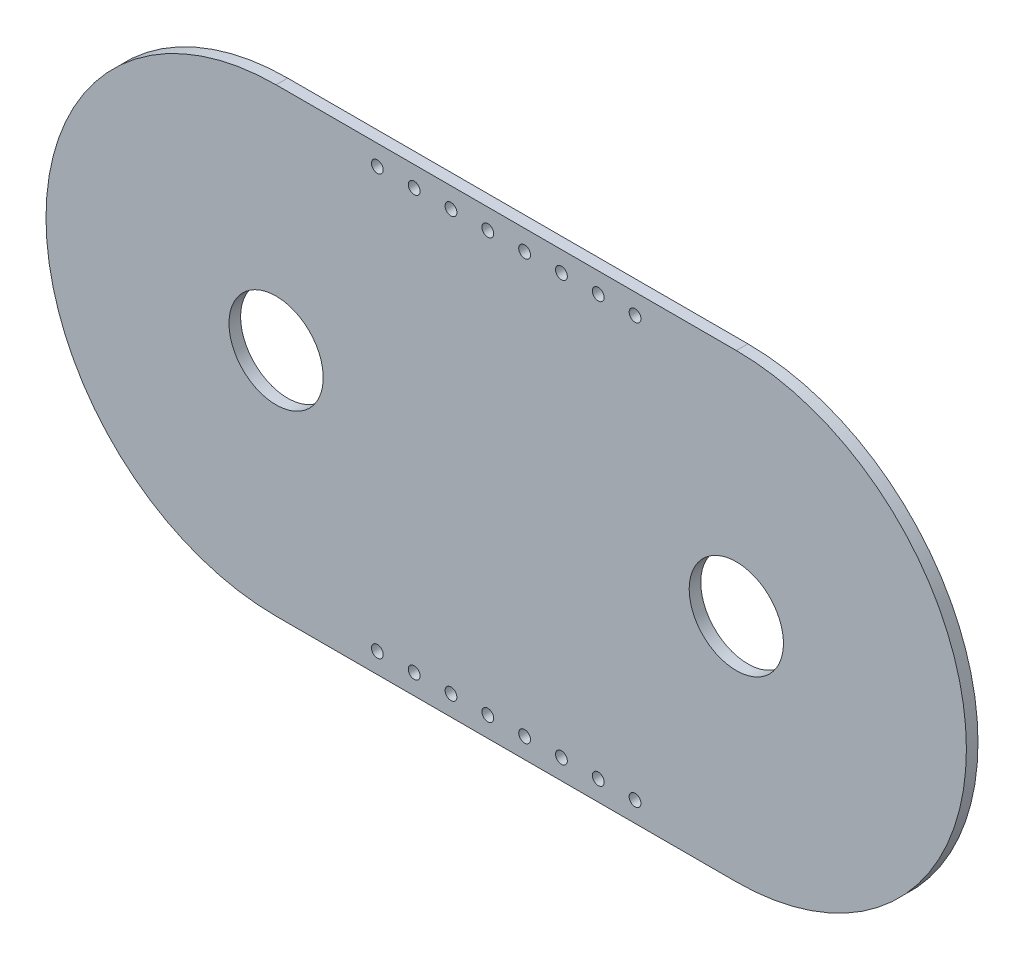
SolidWorks part; units mm, degrees
ref_plane "Front Plane" through (0, 0, 0) normal (0, 0, 1) x (1, 0, 0)
ref_plane "Top Plane" through (0, 0, 0) normal (0, 1, 0) x (1, 0, 0)
ref_plane "Right Plane" through (0, 0, 0) normal (1, 0, 0) x (0, 0, -1)
sketch "Sketch1" plane through (0, 0, 0) normal (0, 0, 1) x (1, 0, 0)
  line L0 (-15.875, 15.875) -> (47.625, 15.875) construction
  line L3 (0, 31.75) -> (31.75, 31.75)
  line L5 (0, 0) -> (31.75, 0)
  line L7 (15.875, 31.75) -> (15.875, 0) construction
  arc A40 (0, 31.75) -> (0, 0) centre (0, 15.875) ccw
  arc A41 (31.75, 0) -> (31.75, 31.75) centre (31.75, 15.875) ccw
  circle A42 centre (0, 15.875) radius 3.2512
  circle A43 centre (31.75, 15.875) radius 3.2512
  point P29 (0, 15.875)
  dimension "D2" = 31.75
  dimension "D4" = 6.5024
  dimension "D1" = 31.75
  dimension "D3" = 6.5024
extrude "Boss-Extrude1" add sketch "Sketch1" along normal blind 0.8 contours L5 A41 L3 A40 A43 A42 region at (15.875, 15.875, 0)
sketch "Sketch3" plane through (0, 0, 0.8) normal (0, 0, -1) x (-1, 0, 0)
  line L0 (0, 0) -> (-31.75, 0) construction
  line L2 (0, 31.75) -> (-31.75, 31.75) construction
  line L3 (0, 0) -> (-31.75, 0)
  line L4 (0, 31.75) -> (-31.75, 31.75)
  line L5 (-15.875, 31.75) -> (-15.875, 0) construction
  line L6 (0, 15.875) -> (-33.3089, 15.875) construction
  circle A16 centre (-14.605, 30.353) radius 0.4064
  circle A17 centre (-12.065, 30.353) radius 0.4064
  circle A18 centre (-9.525, 30.353) radius 0.4064
  circle A19 centre (-6.985, 30.353) radius 0.4064
  circle A20 centre (-24.765, 30.353) radius 0.4064
  circle A21 centre (-22.225, 30.353) radius 0.4064
  circle A22 centre (-19.685, 30.353) radius 0.4064
  circle A23 centre (-17.145, 30.353) radius 0.4064
  circle A24 centre (-17.145, 1.397) radius 0.4064
  circle A25 centre (-19.685, 1.397) radius 0.4064
  circle A26 centre (-22.225, 1.397) radius 0.4064
  circle A27 centre (-24.765, 1.397) radius 0.4064
  circle A28 centre (-6.985, 1.397) radius 0.4064
  circle A29 centre (-9.525, 1.397) radius 0.4064
  circle A30 centre (-12.065, 1.397) radius 0.4064
  circle A31 centre (-14.605, 1.397) radius 0.4064
  dimension "D1" = 30.353
  dimension "D2" = 0.8128
  dimension "D3" = 1.27
extrude "Cut-Extrude3" cut sketch "Sketch3" along normal through all contours A19 | A18 | A17 | A16 | A23 | A22 | A21 | A20 | A28 | A29 | A30 | A31 | A24 | A25 | A26 | A27
